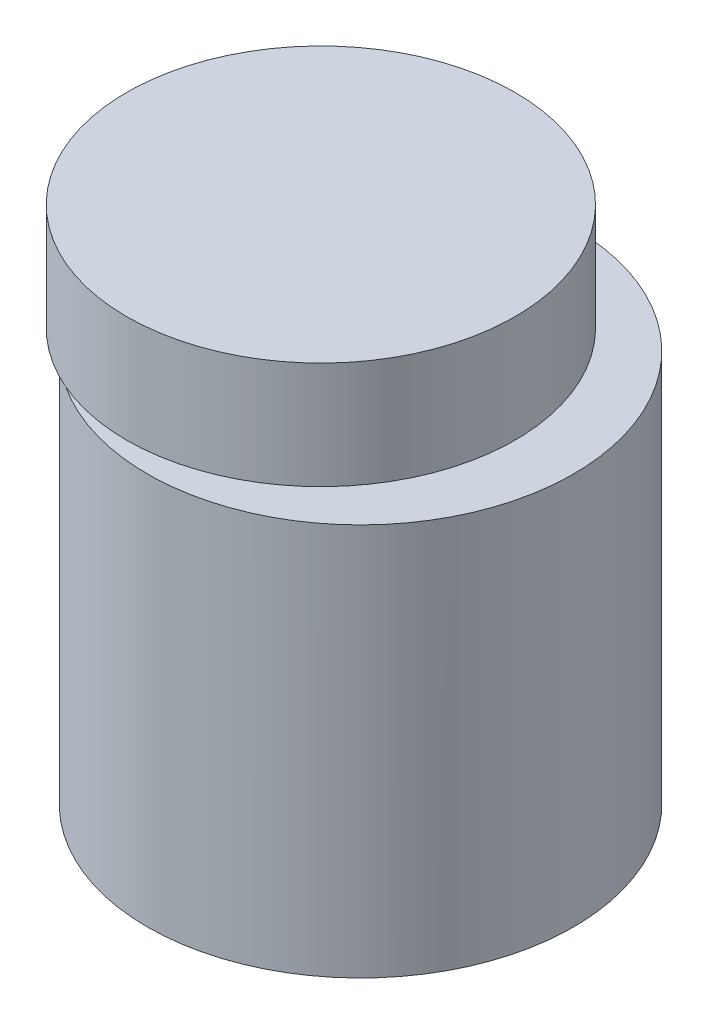
SolidWorks part; units mm, degrees
ref_plane "Ebene vorne" through (0, 0, 0) normal (0, 0, 1) x (1, 0, 0)
ref_plane "Ebene oben" through (0, 0, 0) normal (0, 1, 0) x (1, 0, 0)
ref_plane "Ebene rechts" through (0, 0, 0) normal (1, 0, 0) x (0, 0, -1)
sketch "Skizze1" plane through (0, 0, 0) normal (0, 1, 0) x (1, 0, 0)
  circle A0 centre (0, 0) radius 5.375
  dimension "D1" = 10.75
extrude "Aufsatz-Linear austragen1" add sketch "Skizze1" along normal blind 10
sketch "Skizze2" plane through (0, 0, 0) normal (0, -1, 0) x (-1, 0, 0)
  line L0 (1, -5.2812) -> (1, 5.2812)
  line L1 (-5.375, 0) -> (5.375, 0)
  circle A0 centre (0, 0) radius 5.375 construction
  dimension "D1" = 0
  dimension "D2" = 1
sketch "Skizze3" plane through (0, 0, 0) normal (0, -1, 0) x (-1, 0, 0)
  circle A0 centre (2, 0) radius 5.4
  dimension "D1" = 10.8
  dimension "D2" = 2
extrude "Aufsatz-Linear austragen3" add sketch "Skizze3" along normal blind 10
sketch "Skizze5" plane through (0, -10, 0) normal (0, -1, 0) x (1, 0, 0)
  circle A0 centre (-1, 0) radius 5.4
  circle A1 centre (-2, 0) radius 5.4 construction
  dimension "D2" = 1
  dimension "D3" = 10.8
extrude "Aufsatz-Linear austragen4" add sketch "Skizze5" along normal blind 7.9
sketch "Skizze6" plane through (0, 10, 0) normal (0, 1, 0) x (1, 0, 0)
  circle A1 centre (-1, 0) radius 4.9
  dimension "D1" = 9.8
  dimension "D2" = 1
extrude "Aufsatz-Linear austragen5" add sketch "Skizze6" along normal blind 2.7
sketch "Skizze8" plane through (0, -17.9, 0) normal (0, -1, 0) x (1, 0, 0)
  circle A0 centre (-1, 0) radius 2.6
  circle A1 centre (-1, 0) radius 5.4 construction
  dimension "D1" = 5.2
extrude "Schnitt-Linear austragen1" cut sketch "Skizze8" against normal blind 25 contours A0
sketch "Skizze9" plane through (0, 7.1, 0) normal (0, -1, 0) x (-1, 0, 0)
  line L1 (-1.05, -1.5992) -> (-1.6, -1.5992)
  line L2 (-1.05, -1.5992) -> (-1.05, 1.5998)
  line L3 (-1.05, 1.5998) -> (-1.6, 1.5998)
  line L4 (-1.6, -1.5992) -> (-1.6, 1.5998)
  circle A0 centre (1, 0) radius 2.6 construction
  dimension "D2" = 2.6
  dimension "D1" = 0.55
extrude "Aufsatz-Linear austragen6" add sketch "Skizze9" along normal blind 15
ref_axis "Achse1" through (-1, 40.5876, 0) along (0, -1, 0)
sketch "Skizze10" plane through (0, -17.9, 0) normal (0, -1, 0) x (1, 0, 0)
  line L1 (-10.4292, 7.7406) -> (10.3859, 7.7406)
  line L2 (-10.4292, 7.7406) -> (-10.4292, -7.8707)
  line L3 (-10.4292, -7.8707) -> (10.3859, -7.8707)
  line L4 (10.3859, 7.7406) -> (10.3859, -7.8707)
extrude "Schnitt-Linear austragen2" cut sketch "Skizze10" against normal blind 18
